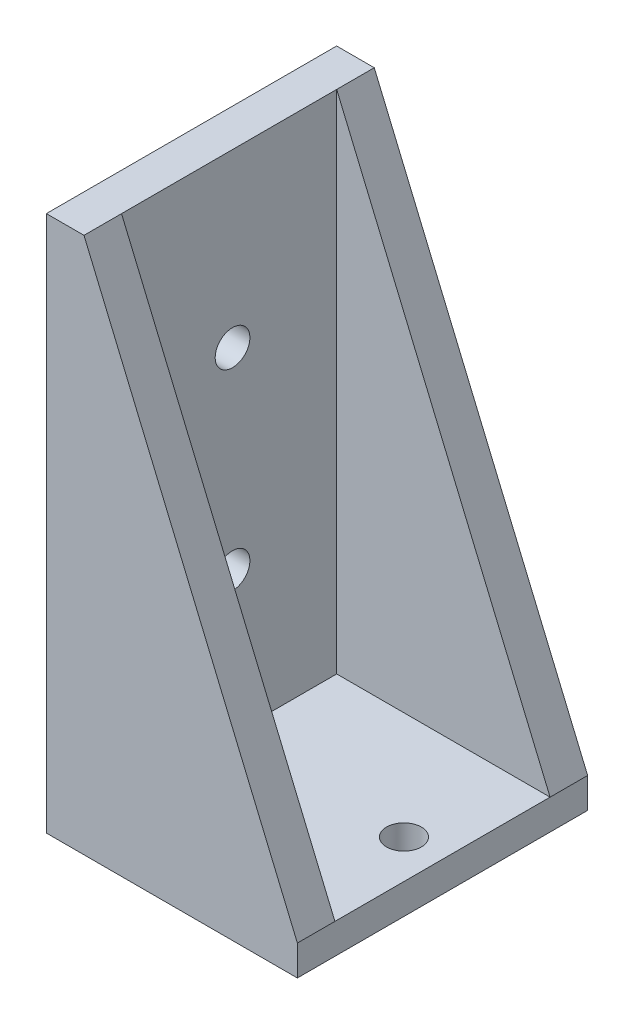
SolidWorks part; units mm, degrees
ref_plane "Front Plane" through (0, 0, 0) normal (0, 0, 1) x (1, 0, 0)
ref_plane "Top Plane" through (0, 0, 0) normal (0, 1, 0) x (1, 0, 0)
ref_plane "Right Plane" through (0, 0, 0) normal (1, 0, 0) x (0, 0, -1)
sketch "Sketch1" plane through (0, 0, 0) normal (0, 0, 1) x (1, 0, 0)
  line L0 (1.8433, 26.29) -> (12.3, 1.4827)
  line L1 (0, 0) -> (12.3, 0)
  line L2 (0, 0) -> (0, 26.29)
  line L3 (0, 26.29) -> (1.8433, 26.29)
  line L4 (12.3, 0) -> (12.3, 1.4827)
  dimension "D1" = 12.3
  dimension "D2" = 26.29
extrude "Boss-Extrude1" add sketch "Sketch1" along normal blind 14.224
sketch "Sketch2" plane through (0, 26.29, 0) normal (0, 1, 0) x (1, 0, 0)
  line L0 (1.8433, -14.224) -> (1.8433, 0) construction
  line L1 (1.8433, -1.84) -> (12.3, -1.84)
  line L2 (1.8433, -1.84) -> (1.8433, -12.384)
  line L3 (1.8433, -12.384) -> (12.3, -12.384)
  line L4 (12.3, -1.84) -> (12.3, -12.384)
  line L5 (1.8433, 0) -> (0, 0) construction
  line L7 (1.8433, 0) -> (1.8433, -1.84) construction
  line L8 (1.8433, -12.384) -> (1.8433, -14.224) construction
  line L9 (12.3, -14.224) -> (12.3, 0) construction
  dimension "D1" = 1.84
  dimension "D2" = 0
extrude "Cut-Extrude1" cut sketch "Sketch2" against normal up to vertex (24.8073 mm away) up to point (12.3, 1.4827, 14.224)
sketch "Sketch3" plane through (0, 0, 0) normal (-1, 0, 0) x (0, 0, 1)
  line L0 (7.9629, 0) -> (6.2611, 0) construction
  line L1 (7.9629, 0) -> (6.2611, 0) construction
  line L2 (7.9629, 0) -> (6.2611, 0)
  line L3 (7.9629, 0) -> (6.2611, 0)
  circle A0 centre (6.944, 17.8835) radius 0.8509 construction
  circle A1 centre (6.944, 8.4171) radius 0.8509 construction
  circle A2 centre (6.944, 17.8835) radius 0.8509
  circle A3 centre (6.944, 8.4171) radius 0.8509
extrude "Cut-Extrude2" cut sketch "Sketch3" against normal blind 10 contours A2 | A3 region at (0, 17.8835, 6.944) region at (0, 8.4171, 6.944)
sketch "Sketch4" plane through (0, 0, 0) normal (0, -1, 0) x (1, 0, 0)
  circle A0 centre (10.4099, 7.112) radius 0.8509 construction
  circle A1 centre (0.9436, 7.112) radius 0.8509 construction
  circle A2 centre (10.4099, 7.112) radius 0.8509
  circle A3 centre (0.9436, 7.112) radius 0.8509
extrude "Cut-Extrude3" cut sketch "Sketch4" against normal up to surface (1.4827 mm away) up to face at (7.0717, 1.4827, 7.112)
